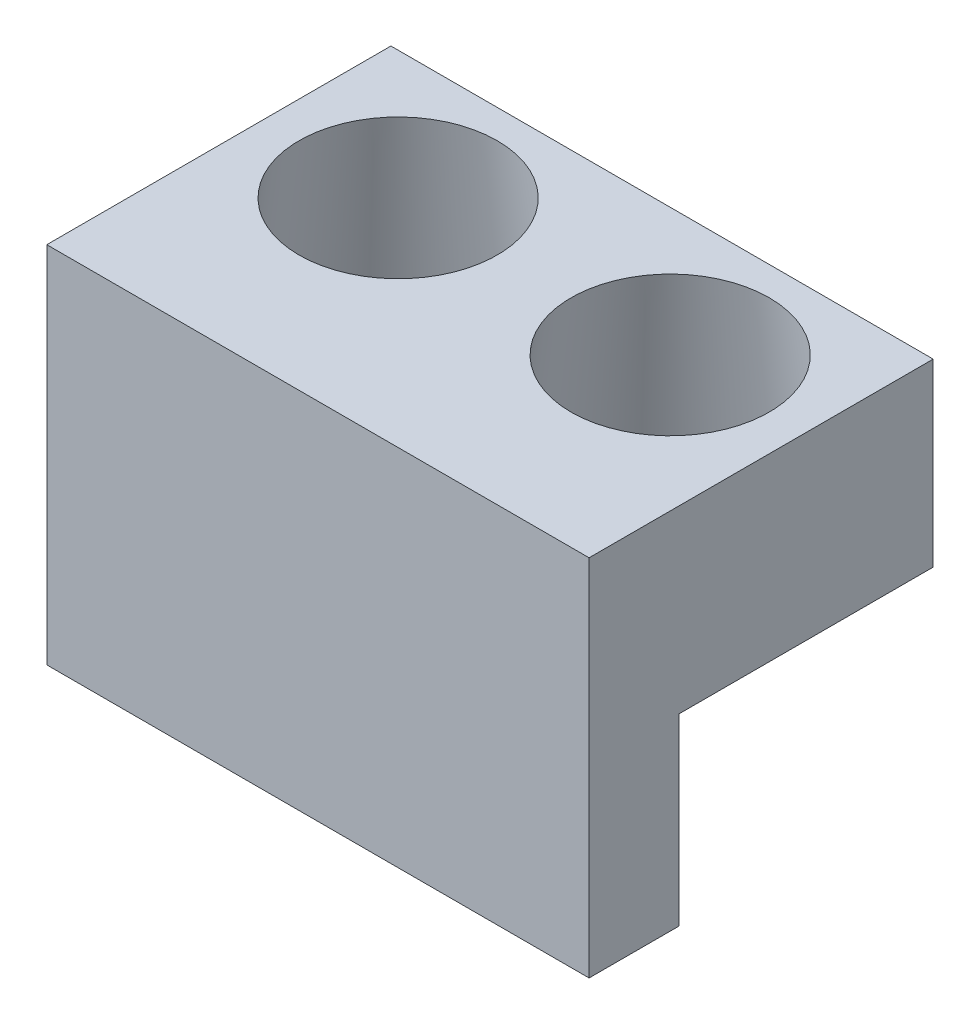
SolidWorks part; units mm, degrees
ref_plane "Front Plane" through (0, 0, 0) normal (0, 0, 1) x (1, 0, 0)
ref_plane "Top Plane" through (0, 0, 0) normal (0, 1, 0) x (1, 0, 0)
ref_plane "Right Plane" through (0, 0, 0) normal (1, 0, 0) x (0, 0, -1)
sketch "Sketch1" plane through (0, 0, 0) normal (0, 1, 0) x (1, 0, 0)
  line L0 (-38.227, 0) -> (38.227, 0)
  line L1 (-38.227, 0) -> (-38.227, -12.7)
  line L2 (-38.227, -12.7) -> (38.227, -12.7)
  line L3 (38.227, -12.7) -> (38.227, 0)
  point P4 (0, 0)
  dimension "D1" = 76.454
  dimension "D2" = 12.7
extrude "Boss-Extrude1" add sketch "Sketch1" along normal blind 51.308
sketch "Sketch2" plane through (0, 51.308, 0) normal (0, 1, 0) x (1, 0, 0)
  line L0 (-38.227, 0) -> (-38.227, 35.814)
  line L1 (-38.227, 35.814) -> (38.227, 35.814)
  line L2 (38.227, 35.814) -> (38.227, 0)
  line L3 (38.227, 0) -> (-38.227, 0) construction
  line L4 (38.227, 0) -> (-38.227, 0)
  dimension "D1" = 35.814
extrude "Boss-Extrude2" add sketch "Sketch2" against normal blind 25.4
sketch "Sketch3" plane through (0, 25.908, 0) normal (0, -1, 0) x (1, 0, 0)
  line L0 (-19.177, -17.78) -> (19.177, -17.78) construction
  line L1 (38.227, -35.814) -> (-38.227, -35.814) construction
  circle A0 centre (-19.177, -17.78) radius 17.145
  circle A1 centre (19.177, -17.78) radius 17.145
  point P3 (0, -17.78)
  dimension "D2" = 34.29
  dimension "D1" = 18.034
  dimension "D3" = 38.354
sketch "Sketch4" plane through (0, 51.308, 0) normal (0, 1, 0) x (1, 0, 0)
  line L1 (-19.177, 17.78) -> (19.177, 17.78) construction
  circle A2 centre (19.177, 17.78) radius 13.97
  circle A4 centre (-19.177, 17.78) radius 13.97
  dimension "D1" = 27.94
loft "Cut-Loft2" cut section "Sketch3" section "Sketch4" start constraint default connector at (3.3453, 25.908, -11.199) connector at (6.5366, 51.308, -11.8319)
loft "Cut-Loft3" cut section "Sketch3<3>" section "Sketch4<3>" connector at (-10.2555, 25.908, -32.421) connector at (-11.9699, 51.308, -29.7474)
sketch "Sketch3<3>" plane through (0, 25.908, 0) normal (0, -1, 0) x (1, 0, 0) same geometry as "Sketch3"
sketch "Sketch4<3>" plane through (0, 51.308, 0) normal (0, 1, 0) x (1, 0, 0) same geometry as "Sketch4"
